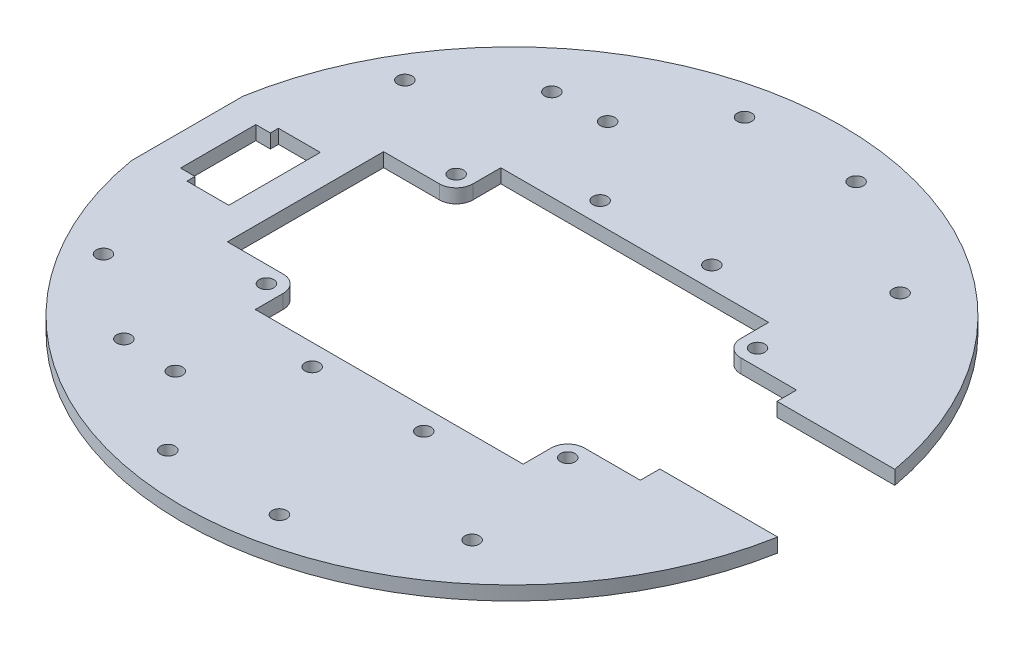
SolidWorks part; units mm, degrees
material "Acrylic (Medium-high impact)"
ref_plane "Front Plane" through (0, 0, 0) normal (0, 0, 1) x (1, 0, 0)
ref_plane "Top Plane" through (0, 0, 0) normal (0, 1, 0) x (1, 0, 0)
ref_plane "Right Plane" through (0, 0, 0) normal (1, 0, 0) x (0, 0, -1)
sketch "Sketch1" plane through (0, 0, 0) normal (0, 1, 0) x (1, 0, 0)
  line L0 (-73.9169, 12.7) -> (-73.9169, -12.7)
  line L2 (-34.29, 21.59) -> (34.29, 21.59) construction
  line L3 (34.29, 21.59) -> (34.29, -21.59) construction
  line L4 (34.29, -21.59) -> (-34.29, -21.59) construction
  line L5 (-34.29, -21.59) -> (-34.29, 21.59) construction
  line L6 (0, 21.59) -> (0, 75) construction
  line L7 (34.29, 0) -> (75, 0) construction
  line L8 (0, -25.4) -> (0, -21.59) construction
  line L9 (-34.29, 0) -> (-38.1, 0) construction
  line L10 (-30.48, 27.94) -> (30.48, 27.94)
  line L11 (-30.48, 27.94) -> (-30.48, 21.59)
  line L12 (0, 21.59) -> (0, 27.94) construction
  line L13 (30.48, 27.94) -> (30.48, 21.59)
  line L14 (34.29, 17.78) -> (46.99, 17.78)
  line L15 (-73.9169, 12.7) -> (-73.9169, -12.7) construction
  line L16 (34.29, -17.78) -> (46.99, -17.78)
  line L17 (46.99, 17.78) -> (46.99, -17.78)
  line L19 (30.48, -21.59) -> (30.48, -27.94)
  line L20 (30.48, -27.94) -> (-30.48, -27.94)
  line L21 (-30.48, -21.59) -> (-30.48, -27.94)
  line L22 (-46.99, -17.78) -> (-34.29, -17.78)
  line L23 (-46.99, -17.78) -> (-46.99, 17.78)
  line L24 (-46.99, 17.78) -> (-34.29, 17.78)
  line L28 (-24.25, -35.9484) -> (24.25, -35.9484) construction
  line L29 (24.25, -35.9484) -> (24.25, -62.4484) construction
  line L30 (-12.7, -35.9484) -> (-12.7, -32.7734) construction
  line L31 (24.25, -62.4484) -> (-24.25, -62.4484) construction
  line L32 (-24.25, -62.4484) -> (-24.25, -35.9484) construction
  line L33 (-24.25, -62.4484) -> (-27.1489, -69.9138) construction
  line L34 (24.25, -62.4484) -> (27.1489, -69.9138) construction
  line L35 (-24.25, -35.9484) -> (-24.25, -27.94) construction
  line L36 (0, -35.9484) -> (0, -62.4484) construction
  line L37 (-54.04, 0) -> (-46.99, 0) construction
  line L38 (-27.425, -49.1984) -> (-24.25, -49.1984) construction
  line L39 (-12.7, -65.6234) -> (-12.7, -62.4484) construction
  line L40 (-66.867, 8.5725) -> (-63.565, 8.5725)
  line L41 (-66.867, 8.5725) -> (-66.867, -8.5725)
  line L42 (-66.867, -8.5725) -> (-63.565, -8.5725)
  line L43 (-54.04, 8.5725) -> (-54.04, -8.5725)
  line L44 (-63.565, 8.5725) -> (-63.565, 10.414)
  line L45 (-63.565, 10.414) -> (-54.04, 10.414)
  line L46 (-54.04, 10.414) -> (-54.04, 8.5725)
  line L47 (-63.565, -8.5725) -> (-63.565, -10.414)
  line L48 (-63.565, -10.414) -> (-54.04, -10.414)
  line L49 (-54.04, -10.414) -> (-54.04, -8.5725)
  line L50 (-66.867, 0) -> (-73.9169, 0) construction
  line L51 (55.1757, 50.8) -> (55.1757, -50.8) construction
  arc A0 (-73.9169, -12.7) -> (-73.9169, 12.7) centre (0, 0) ccw
  arc A1 (55.356, -50.6035) -> (55.356, 50.6035) centre (0, 0) ccw construction
  circle A2 centre (-34.29, 21.59) radius 1.651
  circle A3 centre (34.29, 21.59) radius 1.651
  circle A4 centre (-34.29, -21.59) radius 1.651
  circle A5 centre (34.29, -21.59) radius 1.651
  circle A6 centre (-39.6269, 48.6985) radius 1.651 construction
  circle A7 centre (39.6269, -48.6985) radius 1.651
  circle A8 centre (-39.6269, -48.6985) radius 1.651
  circle A9 centre (-58.6769, -34.29) radius 1.651
  circle A10 centre (-58.6769, 34.29) radius 1.651
  circle A11 centre (-39.6269, 48.6985) radius 1.651
  circle A12 centre (39.6269, 48.6985) radius 1.651
  circle A13 centre (39.6269, -48.6985) radius 1.651 construction
  circle A14 centre (12.7, -65.6234) radius 1.651
  circle A15 centre (12.7, -32.7734) radius 1.651
  circle A16 centre (12.7, 32.7734) radius 1.651
  circle A17 centre (12.7, 65.6234) radius 1.651
  arc A18 (-34.29, 17.78) -> (-30.48, 21.59) centre (-34.29, 21.59) ccw
  arc A19 (-34.29, -17.78) -> (-30.48, -21.59) centre (-34.29, -21.59) cw
  arc A20 (30.48, 21.59) -> (34.29, 17.78) centre (34.29, 21.59) ccw
  arc A21 (30.48, -21.59) -> (34.29, -17.78) centre (34.29, -21.59) cw
  circle A22 centre (-27.425, -49.1984) radius 1.651
  circle A23 centre (-12.7, -32.7734) radius 1.651
  circle A24 centre (-12.7, -65.6234) radius 1.651
  circle A25 centre (-12.7, 65.6234) radius 1.651
  circle A26 centre (-27.425, 49.1984) radius 1.651
  circle A27 centre (-12.7, 32.7734) radius 1.651
  dimension "D11" = 3.302
  dimension "D1" = 68.58
  dimension "D2" = 43.18
  dimension "D3" = 3.81
  dimension "D4" = 12.7
  dimension "D5" = 60.96
  dimension "D6" = 35.56
  dimension "D7" = 48.5
  dimension "D8" = 26.5
  dimension "D9" = 12.7
  dimension "D10" = 3.175
  dimension "D12" = 17.145
  dimension "D13" = 6.35
  dimension "D14" = 101.6
  dimension "D15" = 3.302
  dimension "D16" = 20.828
  dimension "D17" = 9.525
extrude "Boss-Extrude1" add sketch "Sketch1" along normal blind 3.175
sketch "Sketch2" plane through (0, 3.175, 0) normal (0, 1, 0) x (1, 0, 0)
  line L0 (46.99, -17.78) -> (46.99, 17.78) construction
  line L1 (46.99, 13.335) -> (73.805, 13.335)
  line L2 (50.3421, 13.335) -> (43.9921, 13.335) construction
  line L3 (46.99, -13.335) -> (73.805, -13.335)
  line L5 (43.9921, -13.335) -> (50.3421, -13.335) construction
  line L6 (46.99, 13.335) -> (46.99, -13.335)
  arc A0 (-73.9169, -12.7) -> (-73.9169, 12.7) centre (0, 0) ccw construction
  arc A1 (73.805, 13.335) -> (73.805, -13.335) centre (0, 0) cw
extrude "Cut-Extrude1" cut sketch "Sketch2" against normal up to surface (3.175 mm away) up to face at (-27.425, 0, -50.8494)
